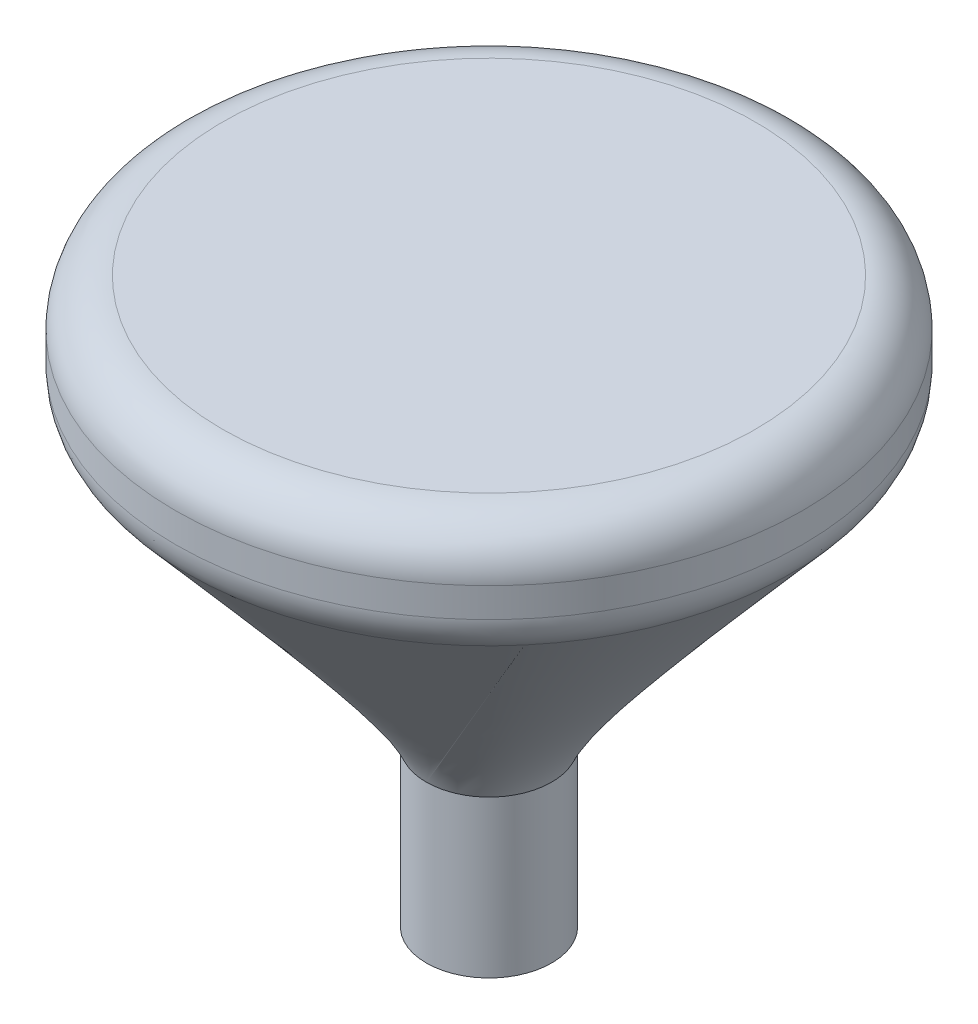
SolidWorks part; units mm, degrees
ref_plane "Front Plane" through (0, 0, 0) normal (0, 0, 1) x (1, 0, 0)
ref_plane "Top Plane" through (0, 0, 0) normal (0, 1, 0) x (1, 0, 0)
ref_plane "Right Plane" through (0, 0, 0) normal (1, 0, 0) x (0, 0, -1)
sketch "Sketch1" plane through (0, 0, 0) normal (0, 1, 0) x (1, 0, 0)
  circle A0 centre (0, 0) radius 2
ref_plane "Plane1" through (0, 15, 0) normal (0, 1, 0) x (1, 0, 0)
sketch "Sketch2" plane through (0, 15, 0) normal (0, 1, 0) x (1, 0, 0)
  circle A0 centre (0, 0) radius 10
extrude "Boss-Extrude1" add sketch "Sketch2" along normal blind 3
extrude "Boss-Extrude2" add sketch "Sketch1" along normal blind 5 separate body
loft "Loft3" add section face at (0, 5, 2) section face at (0, 15, 10) connector at (0.7881, 5, 1.8382) connector at (9.5819, 15, 2.8613)
fillet "Fillet2" radius 1.5 2 edges at (0, 15, 10) (0, 18, 10)
sketch "Sketch3" plane through (0, 0, 0) normal (0, -1, 0) x (1, 0, 0)
  circle A0 centre (0, 0) radius 1
extrude "Cut-Extrude1" cut sketch "Sketch3" against normal blind 15
